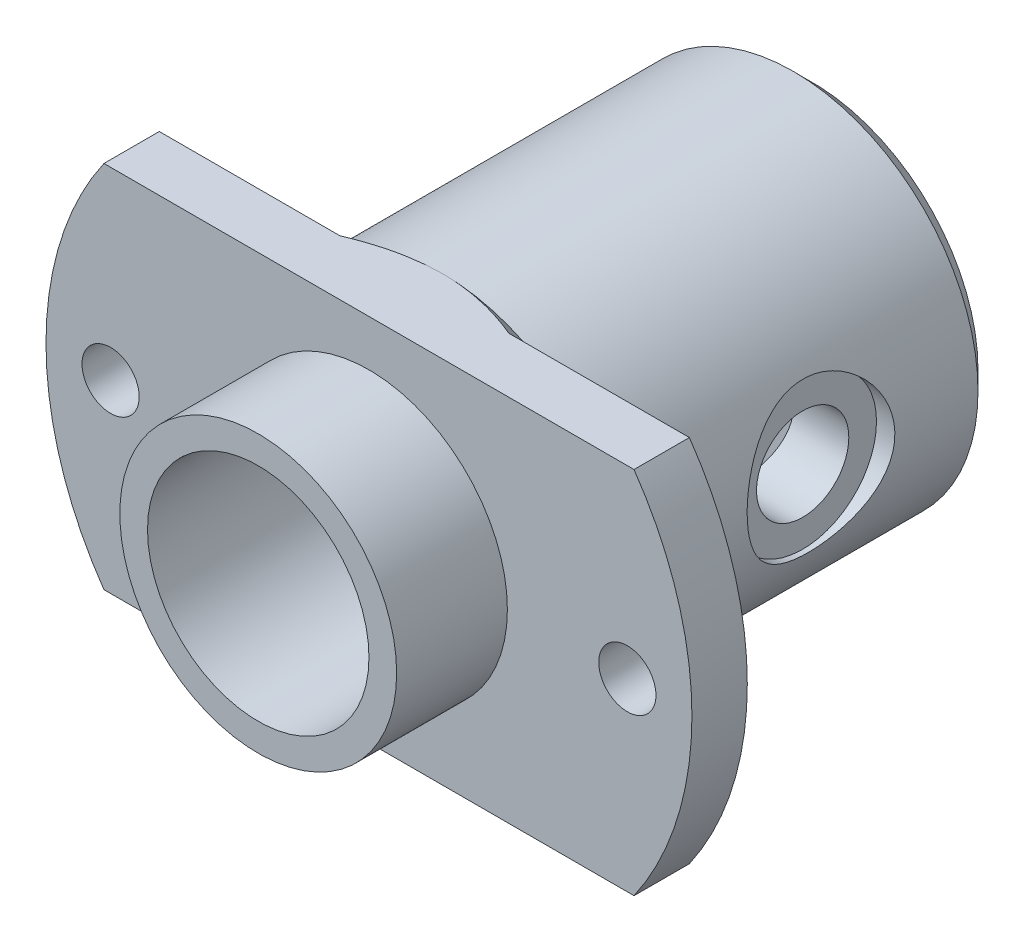
SolidWorks part; units mm, degrees
ref_plane "Front Plane" through (0, 0, 0) normal (0, 0, 1) x (1, 0, 0)
ref_plane "Top Plane" through (0, 0, 0) normal (0, 1, 0) x (1, 0, 0)
ref_plane "Right Plane" through (0, 0, 0) normal (1, 0, 0) x (0, 0, -1)
sketch "Sketch2" plane through (0, 0, 0) normal (0, 0, 1) x (1, 0, 0)
  circle A0 centre (0, 0) radius 10
  dimension "D1" = 20
extrude "Boss-Extrude1" add sketch "Sketch2" along normal blind 21
sketch "Sketch3" plane through (0, 0, 21) normal (0, 0, 1) x (1, 0, 0)
  line L0 (14.3614, 10) -> (-14.3614, 10)
  line L3 (-14.3614, -10) -> (14.3614, -10)
  line L5 (-15.6459, 7.8395) -> (15.6459, -7.8395) construction
  line L6 (-15.6459, -7.8395) -> (15.6459, 7.8395) construction
  arc A0 (-14.3614, 10) -> (-14.3614, -10) centre (0, 0) ccw
  arc A1 (14.3614, -10) -> (14.3614, 10) centre (0, 0) ccw
  circle A2 centre (14, 0) radius 1.55
  circle A3 centre (-14, 0) radius 1.55
  dimension "D1" = 35
  dimension "D2" = 3.1
  dimension "D3" = 3.1
  dimension "D4" = 14
  dimension "D5" = 14
extrude "Boss-Extrude3" add sketch "Sketch3" along normal blind 3
sketch "Sketch4" plane through (0, 0, 24) normal (0, 0, 1) x (1, 0, 0)
  circle A0 centre (0, 0) radius 7.5
  dimension "D1" = 15
extrude "Boss-Extrude4" add sketch "Sketch4" along normal blind 6
sketch "Sketch5" plane through (0, 0, 30) normal (0, 0, 1) x (1, 0, 0)
  circle A0 centre (0, 0) radius 6
  dimension "D1" = 12
extrude "Cut-Extrude1" cut sketch "Sketch5" against normal blind 25
ref_plane "Plane1" through (10, 0, 0) normal (1, 0, 0) x (0, 0, -1)
sketch "Sketch6" plane through (10, 0, 0) normal (1, 0, 0) x (0, 0, -1)
  line L0 (-30, 7.5) -> (-30, -7.5) construction
  circle A0 centre (-9.5, 0.3232) radius 4
  dimension "D1" = 8
  dimension "D2" = 20.5
extrude "Cut-Extrude2" cut sketch "Sketch6" against normal blind 1
sketch "Sketch7" plane through (9, 0, 0) normal (1, 0, 0) x (0, 0, -1)
  circle A0 centre (-9.5, 0.3232) radius 2.5
  dimension "D1" = 5
extrude "Cut-Extrude3" cut sketch "Sketch7" against normal blind 7
chamfer "Chamfer1" distance 1 angle 45 1 edges at (10, 0, 0)
chamfer "Chamfer2" distance 1 angle 45 2 edges at (10, 0, 21) (-10, 0, 21)
